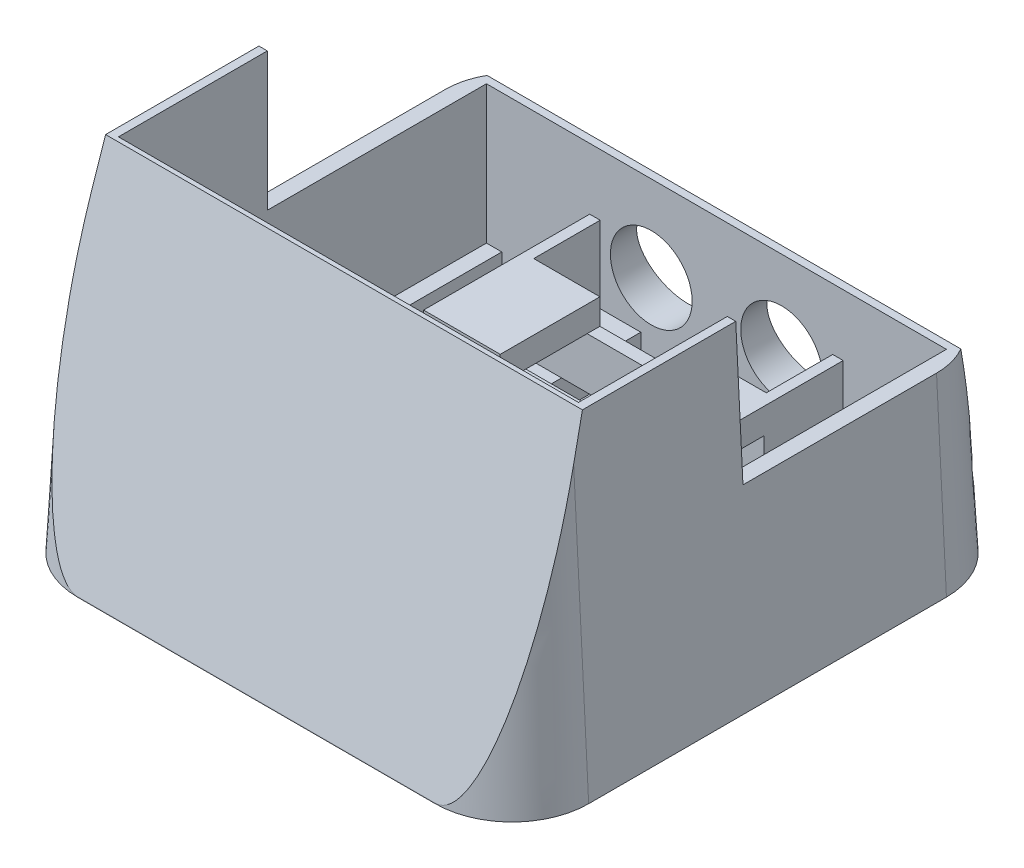
SolidWorks part; units mm, degrees
ref_plane "Front Plane" through (0, 0, 0) normal (0, 0, 1) x (1, 0, 0)
ref_plane "Top Plane" through (0, 0, 0) normal (0, 1, 0) x (1, 0, 0)
ref_plane "Right Plane" through (0, 0, 0) normal (1, 0, 0) x (0, 0, -1)
sketch "Sketch1" plane through (0, 0, 0) normal (0, 1, 0) x (1, 0, 0)
  line L0 (-35, 50) -> (35, 50)
  line L5 (50, 35) -> (50, -35)
  line L6 (-50, 35) -> (-50, -35)
  line L7 (-35, -50) -> (35, -50)
  arc A0 (35, -50) -> (50, -35) centre (35, -35) ccw
  arc A1 (-50, -35) -> (-35, -50) centre (-35, -35) ccw
  arc A2 (-50, 35) -> (-35, 50) centre (-35, 35) cw
  arc A3 (35, 50) -> (50, 35) centre (35, 35) cw
  point P14 (0, -50)
  point P19 (-50, 0)
  dimension "D3" = 15
  dimension "D4" = 15
  dimension "D5" = 15
  dimension "D6" = 15
  dimension "D1" = 100
  dimension "D2" = 100
extrude "Boss-Extrude1" add sketch "Sketch1" along normal blind 10
sketch "Sketch2" plane through (0, 10, 0) normal (0, 1, 0) x (1, 0, 0)
  line L0 (-50, 35) -> (-50, -35) construction
  line L1 (-42, 40) -> (-24.8, 40)
  line L2 (-42, 40) -> (-42, -3)
  line L3 (-42, -3) -> (-24.8, -3)
  line L4 (-24.8, 40) -> (-24.8, -3)
  line L5 (-42, 40) -> (-24.8, -3) construction
  line L6 (-42, -3) -> (-24.8, 40) construction
  line L7 (24.8, 40) -> (42, 40)
  line L8 (24.8, 40) -> (24.8, -3)
  line L9 (24.8, -3) -> (42, -3)
  line L10 (42, 40) -> (42, -3)
  line L11 (24.8, 40) -> (42, -3) construction
  line L12 (24.8, -3) -> (42, 40) construction
  line L13 (50, -35) -> (50, 35) construction
  line L15 (35, 50) -> (-35, 50) construction
  point P0 (-33.4, 18.5)
  point P5 (33.4, 18.5)
  dimension "D1" = 8
  dimension "D2" = 8
  dimension "D3" = 17.2
  dimension "D4" = 17.2
  dimension "D5" = 43
  dimension "D6" = 43
  dimension "D7" = 10
  dimension "D8" = 10
extrude "Cut-Extrude1" cut sketch "Sketch2" against normal through all
sketch "Sketch3" plane through (0, 10, 0) normal (0, 1, 0) x (1, 0, 0)
  line L1 (-40, -8) -> (40, -8)
  line L2 (-40, -8) -> (-40, -32)
  line L3 (-40, -32) -> (40, -32)
  line L4 (40, -8) -> (40, -32)
  line L5 (-40, -8) -> (40, -32) construction
  line L6 (-40, -32) -> (40, -8) construction
  line L7 (-45, -3) -> (45, -3)
  line L8 (-45, -3) -> (-45, -37)
  line L9 (-45, -37) -> (45, -37)
  line L10 (45, -3) -> (45, -37)
  line L11 (-45, -3) -> (45, -37) construction
  line L12 (-45, -37) -> (45, -3) construction
  line L13 (-35, -50) -> (35, -50) construction
  line L14 (-42, -3) -> (-24.8, -3) construction
  point P0 (0, -20)
  point P5 (0, -20)
  point P18 (0, -50)
  dimension "D1" = 24
  dimension "D2" = 80
  dimension "D3" = 34
  dimension "D4" = 90
extrude "Boss-Extrude3" add sketch "Sketch3" along normal blind 15
sketch "Sketch4" plane through (0, 10, 0) normal (0, 1, 0) x (1, 0, 0)
  line L0 (24.8, 40) -> (24.8, -3) construction
  line L3 (-24.8, 12.5) -> (24.8, 12.5)
  line L5 (-24.8, 24.5) -> (24.8, 24.5)
  line L6 (-24.8, 29.5) -> (24.8, 29.5)
  line L11 (-24.8, 7.5) -> (24.8, 7.5)
  line L12 (-24.8, 29.5) -> (-24.8, 24.5)
  line L13 (-24.8, -3) -> (-24.8, 40) construction
  line L14 (-24.8, 12.5) -> (-24.8, 7.5)
  line L15 (24.8, 12.5) -> (24.8, 7.5)
  line L16 (24.8, 29.5) -> (24.8, 24.5)
  point P4 (-24.8, 18.5)
  dimension "D1" = 5
  dimension "D2" = 12
  dimension "D3" = 5
  dimension "D4" = 6
extrude "Boss-Extrude4" add sketch "Sketch4" along normal blind 10
sketch "Sketch5" plane through (0, 20, 0) normal (0, 1, 0) x (1, 0, 0)
  line L0 (-24.8, 7.5) -> (24.8, 7.5) construction
  line L1 (-24.8, 29.5) -> (-9.8, 29.5)
  line L2 (-24.8, 29.5) -> (-24.8, 7.5)
  line L3 (-24.8, 7.5) -> (-9.8, 7.5)
  line L4 (-9.8, 29.5) -> (-9.8, 7.5)
  line L6 (24.8, 29.5) -> (9.8, 29.5)
  line L7 (24.8, 29.5) -> (24.8, 7.5)
  line L8 (24.8, 7.5) -> (9.8, 7.5)
  line L9 (9.8, 29.5) -> (9.8, 7.5)
  dimension "D1" = 15
  dimension "D2" = 15
extrude "Boss-Extrude5" add sketch "Sketch5" along normal blind 5
sketch "Sketch6" plane through (0, 10, 0) normal (0, 1, 0) x (1, 0, 0)
  line L1 (-45, -37) -> (45, -37)
  line L2 (-45, -37) -> (-45, 40)
  line L3 (-45, 40) -> (45, 40)
  line L4 (45, -37) -> (45, 40)
  line L5 (45, -37) -> (45, -3) construction
  line L6 (-24.8, 40) -> (-42, 40) construction
  line L7 (-50, 35) -> (-50, -35) construction
  line L8 (-35, -50) -> (35, -50) construction
  line L9 (50, -35) -> (50, 35) construction
  line L10 (35, 50) -> (-35, 50) construction
  line L11 (-50, 35) -> (-50, -35)
  line L12 (-35, -50) -> (35, -50)
  line L13 (50, -35) -> (50, 35)
  line L14 (35, 50) -> (-35, 50)
  arc A0 (-50, -35) -> (-35, -50) centre (-35, -35) ccw construction
  arc A1 (35, -50) -> (50, -35) centre (35, -35) ccw construction
  arc A2 (50, 35) -> (35, 50) centre (35, 35) ccw construction
  arc A3 (-35, 50) -> (-50, 35) centre (-35, 35) ccw construction
  arc A4 (-50, -35) -> (-35, -50) centre (-35, -35) ccw
  arc A5 (35, -50) -> (50, -35) centre (35, -35) ccw
  arc A6 (50, 35) -> (35, 50) centre (35, 35) ccw
  arc A7 (-35, 50) -> (-50, 35) centre (-35, 35) ccw
extrude "Boss-Extrude6" add sketch "Sketch6" along normal up to surface (15 mm away) up to face at (0, 25, 20)
sketch "Sketch9" plane through (0, 25, 0) normal (0, 1, 0) x (1, 0, 0)
  line L22 (-50, 35) -> (-50, -35) construction
  line L23 (-35, -50) -> (35, -50) construction
  line L24 (50, -35) -> (50, 35) construction
  line L25 (35, 50) -> (-35, 50) construction
  line L26 (-45, 35) -> (-45, -35)
  line L27 (-35, -45) -> (35, -45)
  line L28 (45, -35) -> (45, 35)
  line L29 (35, 45) -> (-35, 45)
  line L30 (-45, 35) -> (-45, -32)
  line L32 (45, -32) -> (45, 35)
  line L34 (-50, 35) -> (-50, -35)
  line L35 (-35, -50) -> (35, -50)
  line L36 (50, -35) -> (50, 35)
  line L37 (35, 50) -> (-35, 50)
  line L38 (45, -32) -> (-45, -32)
  line L39 (-40, -32) -> (40, -32) construction
  line L40 (43.6603, 40) -> (-43.6603, 40)
  line L41 (45, 40) -> (-45, 40) construction
  arc A23 (-50, -35) -> (-35, -50) centre (-35, -35) ccw construction
  arc A24 (35, -50) -> (50, -35) centre (35, -35) ccw construction
  arc A25 (50, 35) -> (35, 50) centre (35, 35) ccw construction
  arc A26 (-35, 50) -> (-50, 35) centre (-35, 35) ccw construction
  arc A27 (-45, -35) -> (-35, -45) centre (-35, -35) ccw
  arc A28 (35, -45) -> (45, -35) centre (35, -35) ccw
  arc A29 (45, 35) -> (35, 45) centre (35, 35) ccw
  arc A30 (-35, 45) -> (-45, 35) centre (-35, 35) ccw
  arc A33 (45, 35) -> (43.6603, 40) centre (35, 35) ccw
  arc A34 (-43.6603, 40) -> (-45, 35) centre (-35, 35) ccw
  arc A35 (-50, -35) -> (-35, -50) centre (-35, -35) ccw
  arc A36 (35, -50) -> (50, -35) centre (35, -35) ccw
  arc A37 (50, 35) -> (35, 50) centre (35, 35) ccw
  arc A38 (-35, 50) -> (-50, 35) centre (-35, 35) ccw
  dimension "D1" = 5
extrude "Boss-Extrude8" add sketch "Sketch9" along normal blind 39
chamfer "Chamfer1" distance 64 angle 3 8 edges at (0, 64, 50) (45.6066, 64, 45.6066) (-45.6066, 64, 45.6066) (50, 64, 0) (-50, 64, 0) (45.6066, 64, -45.6066) (-45.6066, 64, -45.6066) (0, 64, -50) first distance on face at (0, 32, 50) first distance on face at (44.0533, 32, 44.0533) first distance on face at (-44.0533, 32, 44.0533) first distance on face at (50, 32, 0) first distance on face at (-50, 32, 0) first distance on face at (44.0533, 32, -44.0533) first distance on face at (-44.0533, 32, -44.0533) first distance on face at (0, 32, -50)
chamfer "Chamfer2" distance 64 angle 10 1 edges at (0, 64, -46.6459) tangent propagation no first distance on face at (0, 32, -48.323)
chamfer "Chamfer3" distance 64 angle 12 1 edges at (0, 64, 46.6459) tangent propagation no first distance on face at (0, 32, 48.323)
sketch "Sketch10" plane through (0, 1.3075, 0) normal (-1, 0, 0) x (0, 0, 1)
  line L0 (-35, 62.6925) -> (32.8702, 62.6925) construction
  line L1 (2.8702, 62.6925) -> (-47.1298, 62.6925)
  line L2 (2.8702, 62.6925) -> (2.8702, 35.6925)
  line L3 (2.8702, 35.6925) -> (-47.1298, 35.6925)
  line L4 (-47.1298, 62.6925) -> (-47.1298, 35.6925)
  dimension "D1" = 50
  dimension "D2" = 27
  dimension "D3" = 30
extrude "Cut-Extrude3" cut sketch "Sketch10" against normal through all and the other way through all
sketch "Sketch15" plane through (0, 0, -40) normal (0, 0, 1) x (1, 0, 0)
  line L1 (12.75, 20.25) -> (-12.75, 20.25) construction
  line L2 (0, -35.2) -> (0, 35.2) construction
  line L3 (24.8, 10) -> (-24.8, 10) construction
  circle A0 centre (-12.75, 20.25) radius 8
  circle A1 centre (12.75, 20.25) radius 8
  point P9 (0, 20.25)
  dimension "D3" = 16
  dimension "D4" = 16
  dimension "D1" = 10.25
  dimension "D5" = 25.5
extrude "Cut-Extrude5" cut sketch "Sketch15" against normal through all
sketch "Sketch17" plane through (0, 0, -29.5) normal (0, 0, -1) x (-1, 0, 0)
  line L8 (-9.8, 25) -> (-24.8, 25)
  line L9 (-24.8, 10) -> (24.8, 10)
  line L10 (-24.8, 10) -> (24.8, 10)
  line L11 (24.8, 10) -> (24.8, 25)
  line L12 (24.8, 25) -> (9.8, 25)
  line L13 (9.8, 25) -> (9.8, 20)
  line L14 (9.8, 20) -> (-9.8, 20)
  line L15 (-9.8, 20) -> (-9.8, 25)
  line L16 (-9.8, 25) -> (-24.8, 25)
  line L20 (24.8, 25) -> (9.8, 25)
  line L21 (9.8, 25) -> (9.8, 20)
  line L22 (9.8, 20) -> (-9.8, 20)
  line L23 (-9.8, 20) -> (-9.8, 25)
  line L24 (24.8, 10) -> (24.8, 25)
  line L25 (-24.8, 25) -> (-24.8, 10)
  line L26 (-24.8, 25) -> (-24.8, 10)
  dimension "D1" = 0
extrude "Cut-Extrude6" cut sketch "Sketch17" against normal blind 2.5
sketch "Sketch18" plane through (0, 0, 0) normal (0, -1, 0) x (1, 0, 0)
  line L1 (-14.8, -40) -> (14.8, -40)
  line L2 (-14.8, -40) -> (-14.8, 3)
  line L3 (-14.8, 3) -> (14.8, 3)
  line L4 (14.8, -40) -> (14.8, 3)
  line L5 (-24.8, 3) -> (-24.8, -40) construction
  line L6 (24.8, -40) -> (24.8, 3) construction
  line L7 (24.8, 3) -> (42, 3) construction
  line L9 (-24.8, -40) -> (-42, -40) construction
  dimension "D1" = 10
  dimension "D2" = 10
extrude "Cut-Extrude7" cut sketch "Sketch18" against normal up to surface (10 mm away) up to face at (0, 10, -18.5)
sketch "Sketch20" plane through (0, 25, 0) normal (0, -1, 0) x (1, 0, 0)
  line L0 (-45, -35) -> (-45, -40) construction
  line L1 (-45, -40) -> (-43.6603, -40) construction
  line L2 (45, -40) -> (45, -35) construction
  line L3 (43.6603, -40) -> (45, -40) construction
  line L4 (-45, -35) -> (-45, -40)
  line L5 (-45, -40) -> (-43.6603, -40)
  line L6 (45, -40) -> (45, -35)
  line L7 (43.6603, -40) -> (45, -40)
  arc A0 (-45, -35) -> (-43.6603, -40) centre (-35, -35) ccw construction
  arc A1 (43.6603, -40) -> (45, -35) centre (35, -35) ccw construction
  arc A2 (-45, -35) -> (-43.6603, -40) centre (-35, -35) ccw
  arc A3 (43.6603, -40) -> (45, -35) centre (35, -35) ccw
extrude "Cut-Extrude8" cut sketch "Sketch20" against normal blind 15
sketch "Sketch21" plane through (0, 0, 0) normal (0, -1, 0) x (1, 0, 0)
  line L0 (-14.8, 3) -> (-14.8, -40) construction
  line L1 (-14.8, 3) -> (14.8, 3)
  line L2 (-14.8, 3) -> (-14.8, -30)
  line L3 (-14.8, -30) -> (14.8, -30)
  line L4 (14.8, 3) -> (14.8, -30)
  line L5 (14.8, -40) -> (14.8, 3) construction
  line L7 (-14.8, -40) -> (14.8, -40) construction
  line L8 (14.8, 3) -> (-14.8, 3) construction
  dimension "D2" = 10
extrude "Boss-Extrude10" add sketch "Sketch21" against normal blind 4.5
sketch "Sketch23" plane through (0, 10, 0) normal (0, 1, 0) x (1, 0, 0)
  line L0 (-24.8, 27) -> (-9.8, 27) construction
  line L2 (-22.75, 27) -> (-22.75, 40)
  line L4 (22.75, 27) -> (22.75, 40)
  line L5 (24.8, 40) -> (14.8, 40) construction
  line L6 (-24.8, 27) -> (-24.8, 40) construction
  line L7 (24.8, 40) -> (24.8, 27) construction
  line L8 (24.8, 40) -> (24.8, 27)
  line L9 (-24.8, 27) -> (-24.8, 40)
  line L10 (-22.75, 27) -> (-24.8, 27)
  line L11 (22.75, 27) -> (24.8, 27)
  line L12 (24.8, 40) -> (22.75, 40)
  line L13 (-22.75, 40) -> (-24.8, 40)
  dimension "D1" = 45.5
  dimension "D2" = 2.05
extrude "Boss-Extrude11" add sketch "Sketch23" along normal up to surface (15 mm away) up to face at (-17.3, 25, -17.25)
